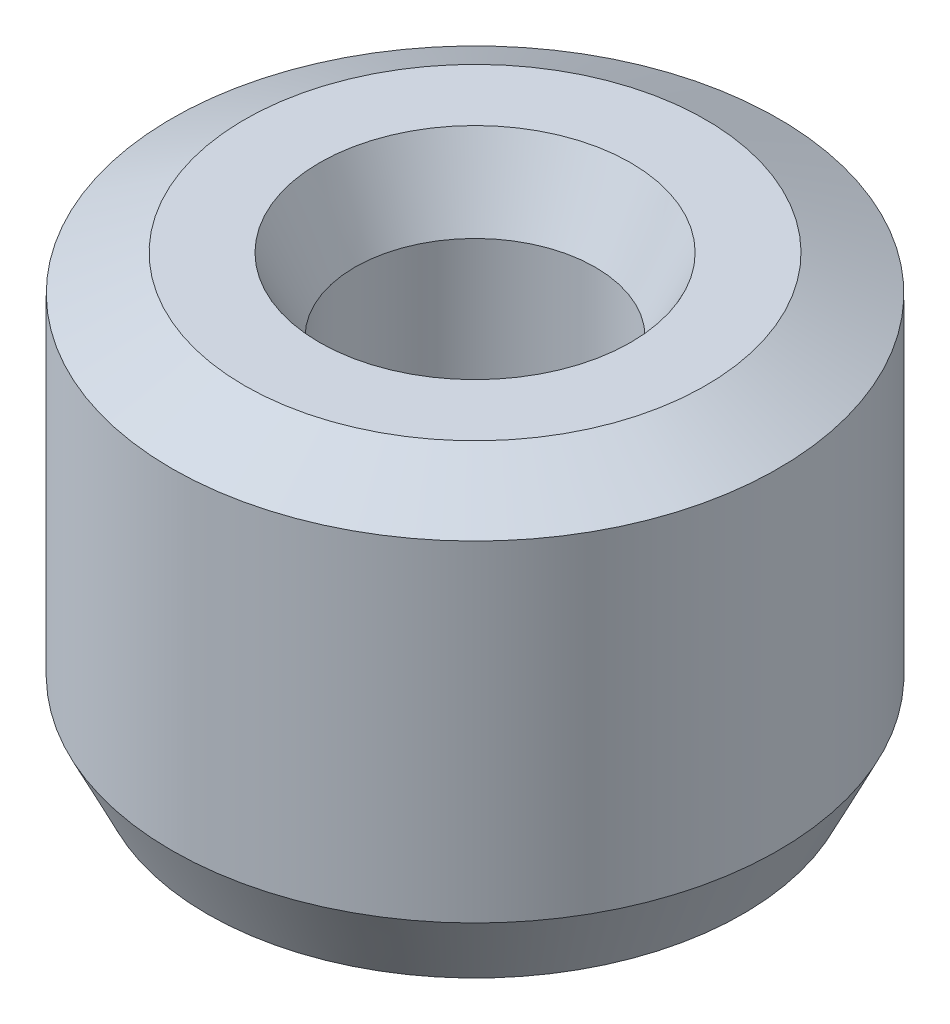
SolidWorks part; units mm, degrees
ref_plane "Front Plane" through (0, 0, 0) normal (0, 0, 1) x (1, 0, 0)
ref_plane "Top Plane" through (0, 0, 0) normal (0, 1, 0) x (1, 0, 0)
ref_plane "Right Plane" through (0, 0, 0) normal (1, 0, 0) x (0, 0, -1)
sketch "Sketch1" plane through (0, 0, 0) normal (0, 1, 0) x (1, 0, 0)
  circle A0 centre (0, 0) radius 12.5
  dimension "SLEEVE_OD" = 25
extrude "Boss-Extrude1" add sketch "Sketch1" along normal blind 18.094
sketch "Sketch2" plane through (0, 0, 0) normal (0, 1, 0) x (1, 0, 0)
  circle A0 centre (0, 0) radius 4.9552
  dimension "BORE_D" = 9.9103
extrude "Cut-Extrude1" cut sketch "Sketch2" along normal through all
chamfer "Chamfer1" distance 1.4605 angle 64.026 4 edges at (0, 18.094, 4.9552) (0, 0, 4.9552) (0, 0, 12.5) (0, 18.094, 12.5) first distance on face at (0, 18.094, 4.9552) first distance on face at (0, 0, 4.9552) first distance on face at (0, 18.094, 12.5)
